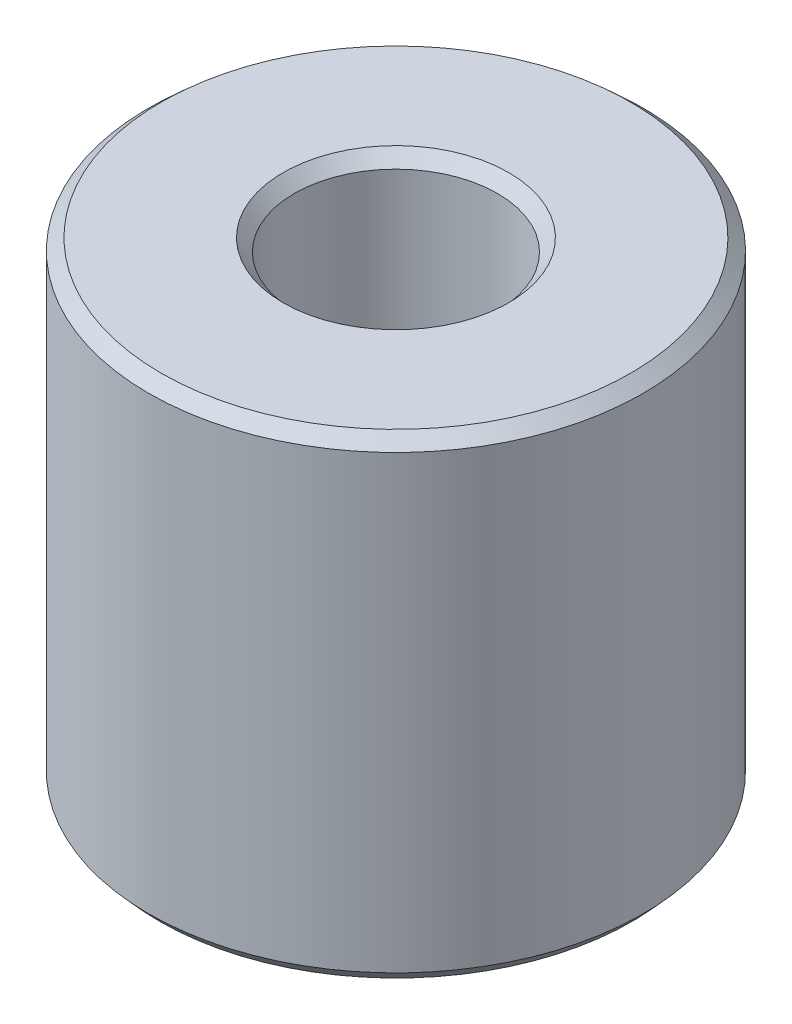
SolidWorks part; units mm, degrees
ref_plane "Front Plane" through (0, 0, 0) normal (0, 0, 1) x (1, 0, 0)
ref_plane "Top Plane" through (0, 0, 0) normal (0, 1, 0) x (1, 0, 0)
ref_plane "Right Plane" through (0, 0, 0) normal (1, 0, 0) x (0, 0, -1)
sketch "Sketch1" plane through (0, 0, 0) normal (0, 1, 0) x (1, 0, 0)
  circle A0 centre (0, 0) radius 57.5
  dimension "SLEEVE_OD" = 115
extrude "Boss-Extrude1" add sketch "Sketch1" along normal blind 110.3506
sketch "Sketch2" plane through (0, 0, 0) normal (0, 1, 0) x (1, 0, 0)
  circle A0 centre (0, 0) radius 23.6162
  dimension "BORE_D" = 47.2324
extrude "Cut-Extrude1" cut sketch "Sketch2" along normal through all
chamfer "Chamfer1" distance 2.6214 angle 47.789 4 edges at (0, 110.3506, 23.6162) (0, 0, 23.6162) (0, 0, 57.5) (0, 110.3506, 57.5) first distance on face at (0, 110.3506, 23.6162) first distance on face at (0, 0, 23.6162) first distance on face at (0, 110.3506, 57.5)
